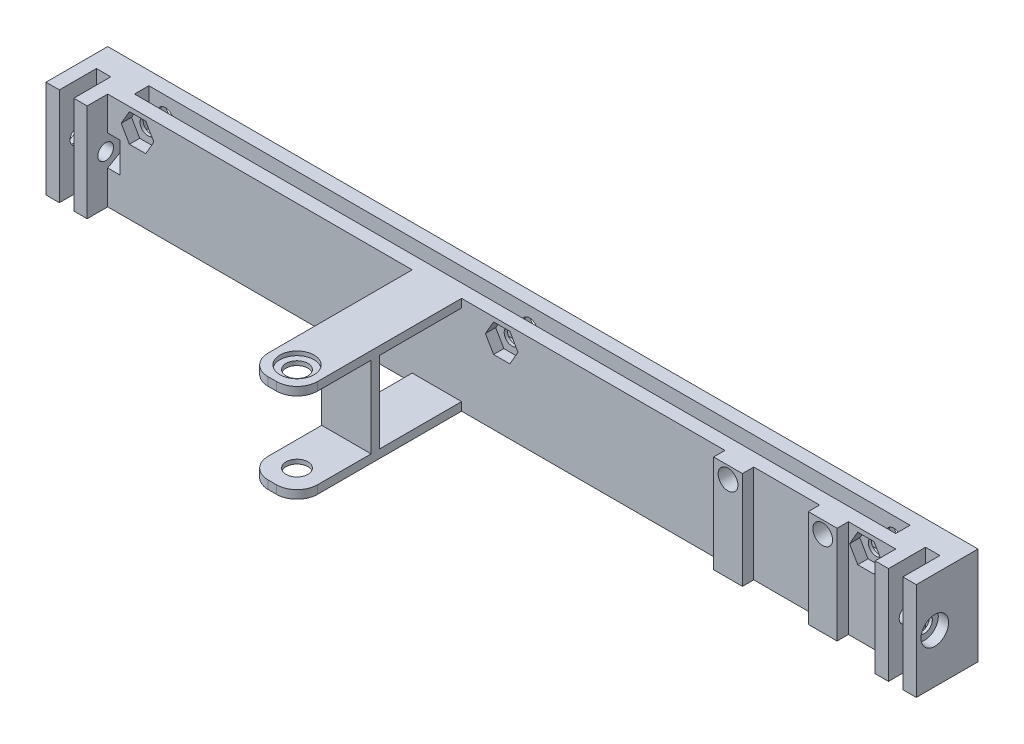
SolidWorks part; units mm, degrees
ref_plane "Front Plane" through (0, 0, 0) normal (1, 0, 0) x (0, 1, 0)
ref_plane "Top Plane" through (0, 0, 0) normal (0, 0, 1) x (0, 1, 0)
ref_plane "Right Plane" through (0, 0, 0) normal (0, 1, 0) x (-1, 0, 0)
sketch "Sketch2" plane through (0, 0, 0) normal (0, 0, 1) x (0, 1, 0)
  line L1 (-71.25, 0) -> (-95, 0)
  line L2 (-71.25, 0) -> (-71.25, 12)
  line L3 (-71.25, 12) -> (-95, 12)
  line L4 (-95, 0) -> (-95, 12)
extrude "Boss-Extrude1" add sketch "Sketch2" along normal blind 10
sketch "Sketch3" plane through (0, 0, 10) normal (0, 0, 1) x (1, 0, 0)
  line L1 (-12, -71.25) -> (0, -71.25)
  line L2 (-12, -71.25) -> (-12, -73.275)
  line L3 (-12, -73.275) -> (0, -73.275)
  line L4 (0, -71.25) -> (0, -73.275)
  line L6 (-12, -73.275) -> (0, -73.275) construction
  dimension "D1" = 2.025
extrude "Boss-Extrude2" add sketch "Sketch3" along normal blind 40
fillet "Fillet1" radius 5 2 edges at (0, -72.2625, 50) (-12, -72.2625, 50)
ref_plane "Plane1" through (0, -83.125, 0) normal (0, 1, 0) x (1, 0, 0)
mirror "Mirror1" about plane through (0, -83.125, 0) normal (0, 1, 0) of "Fillet1", "Boss-Extrude2"
sketch "Sketch5" plane through (0, -95, 0) normal (0, -1, 0) x (1, 0, 0)
  line L1 (-6, 50) -> (-12, 50)
  line L2 (-6, 50) -> (-6, 44)
  line L3 (-6, 44) -> (-12, 44)
  line L4 (-12, 50) -> (-12, 44)
  line L5 (-5, 50) -> (-7, 50) construction
  line L6 (-12, 45) -> (-12, 0) construction
  circle A0 centre (-6, 44) radius 2.65
  dimension "D2" = 5.3
  dimension "D1" = 6
extrude "Cut-Extrude1" cut sketch "Sketch5" against normal through all contours A0
sketch "Sketch6" plane through (0, -95, 0) normal (0, -1, 0) x (1, 0, 0)
  line L1 (-6, 50) -> (-12, 50)
  line L2 (-6, 50) -> (-6, 44)
  line L3 (-6, 44) -> (-12, 44)
  line L4 (-12, 50) -> (-12, 44)
  line L6 (-5, 50) -> (-7, 50) construction
  line L7 (-12, 45) -> (-12, 0) construction
  circle A0 centre (-6, 44) radius 4.15
  dimension "D1" = 6
  dimension "D2" = 8.3
extrude "Cut-Extrude2" cut sketch "Sketch6" against normal blind 1 contours A0
mirror "Mirror2" about plane through (0, -83.125, 0) normal (0, 1, 0) of "Cut-Extrude2"
sketch "Sketch7" plane through (0, 0, 0) normal (0, 0, -1) x (1, 0, 0)
  line L1 (-6, 95) -> (-96, 95)
  line L2 (-6, 95) -> (-6, 71.25)
  line L3 (-6, 71.25) -> (-96, 71.25)
  line L4 (-96, 95) -> (-96, 71.25)
  line L5 (-6, 95) -> (115.5, 95)
  line L6 (-6, 95) -> (-6, 71.25)
  line L7 (-6, 71.25) -> (115.5, 71.25)
  line L8 (115.5, 95) -> (115.5, 71.25)
  line L10 (-12, 95) -> (0, 95) construction
  line L11 (0, 71.25) -> (-12, 71.25) construction
  line M20 (0, 71.25) -> (0, 95)
  line M22 (-12, 95) -> (-12, 71.25)
  dimension "D1" = 90
  dimension "D2" = 121.5
extrude "Boss-Extrude3" add sketch "Sketch7" against normal blind 10 contours L1 L4 L3 M22 | L8 L5 L7 M20 region at (-54, -83.125, 0) region at (57.75, -83.125, 0)
sketch "Sketch8" plane through (0, 0, 10) normal (0, 0, 1) x (1, 0, 0)
  line L1 (115.5, -71.25) -> (105.5, -71.25)
  line L2 (115.5, -71.25) -> (115.5, -95)
  line L3 (115.5, -95) -> (105.5, -95)
  line L4 (105.5, -71.25) -> (105.5, -95)
  line L6 (-96, -71.25) -> (-86, -71.25)
  line L7 (-96, -71.25) -> (-96, -95)
  line L8 (-96, -95) -> (-86, -95)
  line L9 (-86, -71.25) -> (-86, -95)
  dimension "D1" = 10
  dimension "D2" = 10
extrude "Boss-Extrude4" add sketch "Sketch8" along normal blind 5
sketch "Sketch10" plane through (-12, 0, 0) normal (-1, 0, 0) x (0, -1, 0)
  line L0 (95, 45) -> (95, 10) construction
  line L1 (71.25, 10) -> (95, 10)
  line L2 (71.25, 10) -> (71.25, 12)
  line L3 (71.25, 12) -> (95, 12)
  line L4 (95, 10) -> (95, 12)
  dimension "D1" = 2
extrude "Boss-Extrude5" [suppressed] add sketch "Sketch10" along normal blind 24
sketch "Sketch18" plane through (0, -71.25, 0) normal (0, 1, 0) x (-1, 0, 0)
  line L1 (0, 10) -> (12, 10)
  line L2 (0, 10) -> (0, 30)
  line L3 (0, 30) -> (12, 30)
  line L4 (12, 10) -> (12, 30)
  line L5 (12, 45) -> (12, 10) construction
  line L6 (0, 30) -> (12, 30)
  line L7 (0, 30) -> (0, 32)
  line L8 (0, 32) -> (12, 32)
  line L9 (12, 30) -> (12, 32)
  dimension "D1" = 20
  dimension "D2" = 2
extrude "Boss-Extrude7" add sketch "Sketch18" against normal through all contours L7 L6 L9 L8
sketch "Sketch11" plane through (0, -71.25, 0) normal (0, 1, 0) x (-1, 0, 0)
  line L1 (86, 0) -> (-105.5, 0)
  line L2 (86, 0) -> (86, 10)
  line L3 (86, 10) -> (-105.5, 10)
  line L4 (-105.5, 0) -> (-105.5, 10)
  line L5 (82.75, 6.75) -> (-102.25, 6.75)
  line L6 (-102.25, 3.25) -> (-102.25, 6.75)
  line L7 (82.75, 3.25) -> (-102.25, 3.25)
  line L8 (82.75, 3.25) -> (82.75, 6.75)
  line L12 (96, 0) -> (86, 0)
  line L13 (96, 0) -> (96, 10)
  line L14 (96, 10) -> (86, 10)
  line L15 (86, 0) -> (86, 10)
  dimension "D1" = 3.25
extrude "Cut-Extrude3" cut sketch "Sketch11" against normal blind 9 contours L7 L8 L5 L6 region at (9.75, -71.25, 5)
mirror "Mirror3" about plane through (0, -83.125, 0) normal (0, 1, 0) of "Cut-Extrude3"
sketch "Sketch12" plane through (0, 0, 10) normal (0, 0, 1) x (1, 0, 0)
  line L1 (-86, -71.25) -> (-78.75, -71.25)
  line L2 (-86, -71.25) -> (-86, -75.75)
  line L3 (-86, -75.75) -> (-78.75, -75.75)
  line L4 (-78.75, -71.25) -> (-78.75, -75.75)
  circle A0 centre (-78.75, -75.75) radius 1.9
  circle A1 centre (-78.75, -75.75) radius 3.15
  dimension "D3" = 3.8
  dimension "D4" = 6.3
  dimension "D1" = 7.25
  dimension "D2" = 4.5
extrude "Cut-Extrude4" cut sketch "Sketch12" against normal through all and the other way through all contours A0
sketch "Sketch15" plane through (0, 0, 0) normal (0, 0, 1) x (1, 0, 0)
  circle A0 centre (-78.75, -75.75) radius 3.35
  dimension "D1" = 6.7
extrude "Cut-Extrude5" cut sketch "Sketch15" along normal blind 2.5
sketch "Sketch16" plane through (0, 0, 10) normal (0, 0, 1) x (1, 0, 0)
  line L0 (-82.7119, -75.75) -> (-80.7309, -79.1811)
  line L1 (-82.25, -75.75) -> (-80.5, -78.7811)
  line L2 (-80.5, -78.7811) -> (-77, -78.7811)
  line L3 (-77, -78.7811) -> (-75.25, -75.75)
  line L4 (-75.25, -75.75) -> (-77, -72.7189)
  line L5 (-77, -72.7189) -> (-80.5, -72.7189)
  line L6 (-80.5, -72.7189) -> (-82.25, -75.75)
  line L7 (-80.7309, -79.1811) -> (-76.7691, -79.1811)
  line L8 (-76.7691, -79.1811) -> (-74.7881, -75.75)
  line L9 (-74.7881, -75.75) -> (-76.7691, -72.3189)
  line L10 (-76.7691, -72.3189) -> (-80.7309, -72.3189)
  line L11 (-80.7309, -72.3189) -> (-82.7119, -75.75)
  line L12 (-12, -71.25) -> (-86, -71.25) construction
  circle A0 centre (-78.75, -75.75) radius 3.0311 construction
  circle M23 centre (-78.75, -75.75) radius 1.9
extrude "Cut-Extrude6" cut sketch "Sketch16" against normal blind 2.5 contours L10 L11 L0 L7 L8 L9 L6 L5 L4 L3 L2 L1 | L5 L6 L1 L2 L3 L4 M23 region at (-81.6306, -74.0869, 10) region at (-81.2948, -74.2808, 10)
pattern_linear "LPattern1" count 3 spacing 88.5 along (1, 0, 0) of "Cut-Extrude4", "Cut-Extrude6", "Cut-Extrude5"
sketch "Sketch14" plane through (0, 0, 10) normal (0, 0, 1) x (1, 0, 0)
  line L0 (0, -95) -> (105.5, -95) construction
  line L1 (105.5, -71.25) -> (94, -71.25)
  line L2 (105.5, -71.25) -> (105.5, -95)
  line L3 (105.5, -95) -> (94, -95)
  line L4 (94, -71.25) -> (94, -95)
  line L6 (94, -71.25) -> (87, -71.25)
  line L7 (94, -71.25) -> (94, -95)
  line L8 (94, -95) -> (87, -95)
  line L9 (87, -71.25) -> (87, -95)
  line L10 (87, -71.25) -> (71, -71.25)
  line L11 (87, -71.25) -> (87, -95)
  line L12 (87, -95) -> (71, -95)
  line L13 (71, -71.25) -> (71, -95)
  line L14 (71, -71.25) -> (64, -71.25)
  line L15 (71, -71.25) -> (71, -95)
  line L16 (71, -95) -> (64, -95)
  line L17 (64, -71.25) -> (64, -95)
  line M22 (105.5, -71.25) -> (0, -71.25)
  line M24 (0, -95) -> (105.5, -95)
  dimension "D1" = 11.5
  dimension "D2" = 7
  dimension "D3" = 16
  dimension "D4" = 7
extrude "Boss-Extrude6" add sketch "Sketch14" along normal blind 2.75 contours L17 L13 M22 M24 | L9 L4 M22 M24 region at (90.5, -83.125, 10) region at (67.5, -83.125, 10)
sketch "Sketch19" plane through (0, -83.125, 0) normal (0, 1, 0) x (1, 0, 0)
  line L1 (0, -10) -> (40, -10)
  line L2 (0, -10) -> (0, -37)
  line L3 (0, -37) -> (40, -37)
  line L4 (40, -10) -> (40, -37)
  dimension "D1" = 27
  dimension "D2" = 40
extrude "Boss-Extrude8" [suppressed] add sketch "Sketch19" against normal blind 1 and the other way blind 1
sketch "Sketch21" plane through (0, -71.25, 0) normal (0, 1, 0) x (-1, 0, 0)
  line L0 (-112.25, 6) -> (-108.75, 6)
  line L1 (-115.5, 15) -> (-112.25, 15)
  line L2 (-115.5, 15) -> (-115.5, 6)
  line L3 (-115.5, 6) -> (-112.25, 6)
  line L4 (-112.25, 15) -> (-112.25, 6)
  line L5 (-105.5, 15) -> (-108.75, 15)
  line L6 (-105.5, 15) -> (-105.5, 6)
  line L7 (-105.5, 6) -> (-108.75, 6)
  line L8 (-108.75, 15) -> (-108.75, 6)
  line M22 (-105.5, 15) -> (-115.5, 15)
  dimension "D2" = 3.25
  dimension "D3" = 3.25
  dimension "D4" = 9
extrude "Cut-Extrude7" cut sketch "Sketch21" against normal up to next contours L8 L4 L0 M22 region at (110.5, -71.25, 10.5)
pattern_linear "LPattern2" count 2 spacing 201.5 along (-1, 0, 0) of "Cut-Extrude7"
sketch "Sketch22" plane through (0, 0, 12.75) normal (0, 0, 1) x (1, 0, 0)
  line L1 (94, -71.25) -> (90.5, -71.25)
  line L2 (94, -71.25) -> (94, -74.25)
  line L3 (94, -74.25) -> (90.5, -74.25)
  line L4 (90.5, -71.25) -> (90.5, -74.25)
  circle A0 centre (90.5, -74.25) radius 2.4
extrude "Cut-Extrude8" cut sketch "Sketch22" against normal blind 3.8 contours A0
sketch "Sketch26" plane through (0, 0, 8.95) normal (0, 0, 1) x (1, 0, 0)
  circle A0 centre (90.5, -74.25) radius 1.75
extrude "Cut-Extrude12" cut sketch "Sketch26" against normal blind 0.6 contours A0
pattern_linear "LPattern3" count 2 spacing 23 along (-1, 0, 0) of "Cut-Extrude8", "Cut-Extrude12"
sketch "Sketch23" plane through (115.5, 0, 0) normal (1, 0, 0) x (0, 1, 0)
  line L0 (-95, 15) -> (-71.25, 15) construction
  line L1 (-95, 15) -> (-83.125, 15)
  line L2 (-95, 15) -> (-95, 10.5)
  line L3 (-95, 10.5) -> (-83.125, 10.5)
  line L4 (-83.125, 15) -> (-83.125, 10.5)
  circle A0 centre (-83.125, 10.5) radius 1.9
  dimension "D2" = 3.8
  dimension "D1" = 4.5
extrude "Cut-Extrude9" cut sketch "Sketch23" against normal blind 10 contours A0
sketch "Sketch24" plane through (115.5, 0, 0) normal (1, 0, 0) x (0, 1, 0)
  circle A0 centre (-83.125, 10.5) radius 3.35
  dimension "D1" = 6.7
extrude "Cut-Extrude10" cut sketch "Sketch24" against normal blind 2.5
sketch "Sketch25" plane through (105.5, 0, 0) normal (-1, 0, 0) x (0, -1, 0)
  line L0 (71.25, 15) -> (95, 15) construction
  line L1 (81.375, 13.5311) -> (79.625, 10.5)
  line L2 (79.625, 10.5) -> (81.375, 7.4689)
  line L3 (81.375, 7.4689) -> (84.875, 7.4689)
  line L4 (84.875, 7.4689) -> (86.625, 10.5)
  line L5 (86.625, 10.5) -> (84.875, 13.5311)
  line L6 (84.875, 13.5311) -> (81.375, 13.5311)
  line L7 (81.1441, 13.9311) -> (79.1631, 10.5)
  line L8 (79.1631, 10.5) -> (81.1441, 7.0689)
  line L9 (81.1441, 7.0689) -> (85.1059, 7.0689)
  line L10 (85.1059, 7.0689) -> (87.0869, 10.5)
  line L11 (87.0869, 10.5) -> (85.1059, 13.9311)
  line L12 (85.1059, 13.9311) -> (81.1441, 13.9311)
  circle A0 centre (83.125, 10.5) radius 3.0311 construction
extrude "Cut-Extrude11" cut sketch "Sketch25" along normal blind 3 contours L11 L12 L7 L8 L9 L10
ref_plane "Plane2" through (9.75, 0, 0) normal (1, 0, 0) x (0, 0, -1)
mirror "Mirror4" about plane through (9.75, 0, 0) normal (1, 0, 0) of "Cut-Extrude9", "Cut-Extrude11", "Cut-Extrude10"
equation "\"whitekey_cutout_length\"= 101.5"
equation "\"wall_thickness\"=10"
equation "\"base_mount_height\"=40"
equation "\"D1@Boss-Extrude2\"=\"base_mount_height\""
equation "\"D1@Sketch7\"=\"base_rear_length\"+\"wall_thickness\""
equation "\"D2@Sketch7\"=\"wall_thickness\"+\"base_front_length\""
equation "\"base_rear_length\"=80"
equation "\"D1@Boss-Extrude3\"=\"wall_thickness\""
equation "\"D1@Sketch8\"=\"wall_thickness\""
equation "\"D2@Sketch8\"=\"wall_thickness\""
equation "\"dowel_recess_offset\"=3.25"
equation "\"D1@Sketch11\"=\"dowel_recess_offset\""
equation "\"dowel_recess_depth\"=9"
equation "\"D1@Cut-Extrude3\"=\"dowel_recess_depth\""
equation "\"guide_brace_height\"=20"
equation "\"D1@Sketch18\"=\"guide_brace_height\""
equation "\"guide_brace_thickness\"=2"
equation "\"D2@Sketch18\"=\"guide_brace_thickness\""
equation "\"D3@LPattern1\"=0.5*(\"base_front_length\"+\"base_rear_length\"-\"screw_hole_wall_offset\"*2)"
equation "\"base_front_length\"=111.5"
equation "\"screw_hole_wall_offset\"=7.25"
equation "\"screw_hole_edge_inset\"=4.5"
equation "\"D1@Sketch12\"=\"screw_hole_wall_offset\""
equation "\"D2@Sketch12\"=\"screw_hole_edge_inset\""
equation "\"screw_hole_diameter\"=3.8"
equation "\"screw_head_hole_diameter\"=6.7"
equation "\"screw_nut_hole_side_len\"=3.5"
equation "\"D3@Sketch12\"=\"screw_hole_diameter\""
equation "\"D1@Sketch15\"=\"screw_head_hole_diameter\""
equation "\"D1@Sketch16\"=\"screw_nut_hole_side_len\""
equation "\"D1@Boss-Extrude6\"=6-\"dowel_recess_offset\""
equation "\"D1@Sketch21\"=\"dowel_recess_depth\""
equation "\"D2@Sketch21\"=\"dowel_recess_offset\""
equation "\"D3@Sketch21\"=\"dowel_recess_offset\""
equation "\"D4@Sketch21\"=\"dowel_recess_depth\""
equation "\"D3@LPattern2\"=\"base_front_length\"+\"base_rear_length\"+\"wall_thickness\""
equation "\"key_mount_recess_length\"=50"
equation "\"key_mount_recess_height\"=12.5"
equation "\"key_mount_recess_depth\"=1.5"
equation "\"screw_shaft_diameter\"=3.5"
equation "\"switch_board_width\"=30"
equation "\"D2@Sketch14\"=\"screw_shaft_diameter\"*2"
equation "\"D4@Sketch14\"=\"screw_shaft_diameter\"*2"
equation "\"D3@Sketch14\"=\"switch_board_width\"-\"screw_shaft_diameter\"*4"
equation "\"heatset_insert_hole_diameter\"=4.8"
equation "\"heatset_insert_hole_depth\"=3.8"
equation "\"D2@Sketch22\"=\"heatset_insert_hole_diameter\""
equation "\"D1@Cut-Extrude8\"=\"heatset_insert_hole_depth\""
equation "\"D3@LPattern3\"=\"switch_board_width\"-\"screw_shaft_diameter\"*2"
equation "\"switch_board_wall_offset\"=11.5"
equation "\"D1@Sketch14\"=\"switch_board_wall_offset\""
equation "\"D1@Sketch23\"=\"screw_hole_edge_inset\""
equation "\"D2@Sketch23\"=\"screw_hole_diameter\""
equation "\"D1@Sketch24\"=\"screw_head_hole_diameter\""
equation "\"screw_head_and_nut_recess_depth\"=2.5"
equation "\"D1@Cut-Extrude5\"=\"screw_head_and_nut_recess_depth\""
equation "\"D1@Cut-Extrude6\"=\"screw_head_and_nut_recess_depth\""
equation "\"D1@Cut-Extrude10\"=\"screw_head_and_nut_recess_depth\""
equation "\"D1@Sketch25\"=\"screw_nut_hole_side_len\""
equation "\"screw_nut_recess_offset\"=0.4"
equation "\"D2@Sketch16\"=\"screw_nut_recess_offset\""
equation "\"D2@Sketch25\"=\"screw_nut_recess_offset\""
equation "\"D1@Cut-Extrude11\"=\"screw_head_and_nut_recess_depth\"+0.5"
equation "\"D1@Cut-Extrude9\"=\"wall_thickness\""
equation "\"D1@Sketch26\"=\"screw_shaft_diameter\""
equation "\"switch_board_thickness\"=1.6"
equation "\"front_rear_panel_width\"=23.75"
equation "\"rod_length_adj\"=0.5"
equation "\"rod_insert_length\"=2.8"
equation "\"D1@Cut-Extrude12\"=6-\"heatset_insert_hole_depth\"-\"switch_board_thickness\""
equation "\"rod_diameter\"=5"
equation "\"rod_head_diameter\"=8"
equation "\"switch_black_key_mount_height\"=8"
equation "\"switch_white_key_mount_height\"=3"
equation "\"D2@Sketch5\"=\"rod_diameter\"+0.3"
equation "\"D2@Sketch6\"=\"rod_head_diameter\"+0.3"
